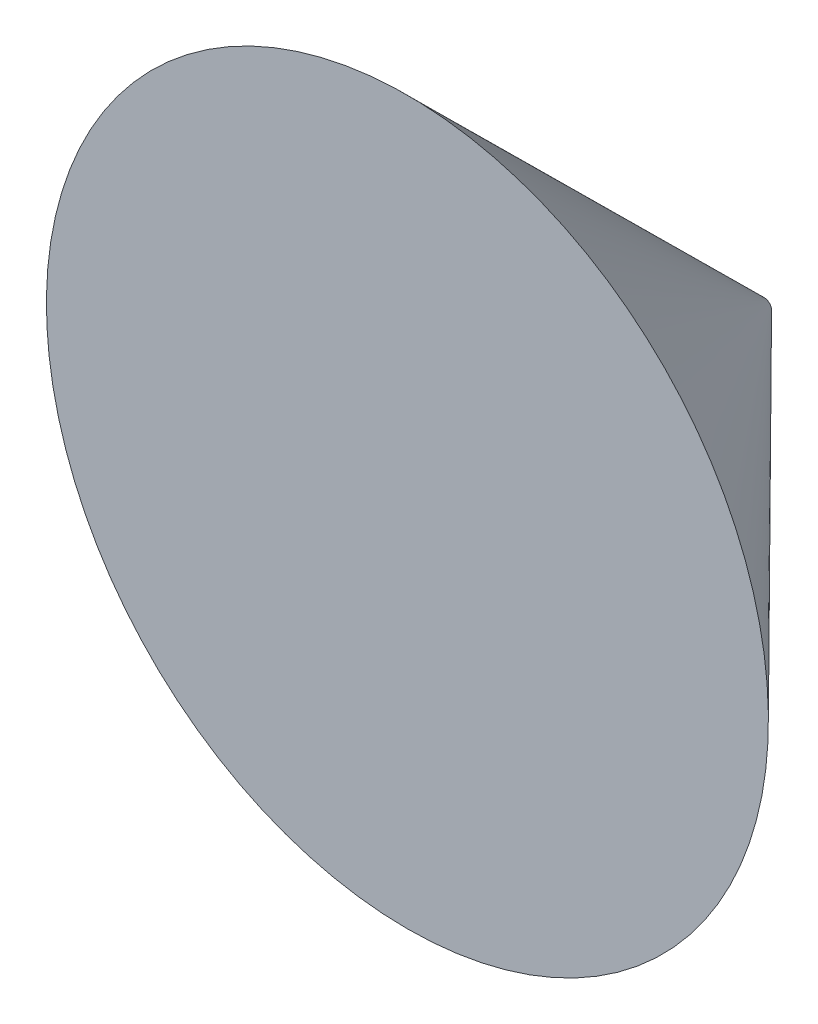
SolidWorks part; units mm, degrees
material "ABS PC"
ref_plane "Front Plane" through (0, 0, 0) normal (0, 0, 1) x (1, 0, 0)
ref_plane "Top Plane" through (0, 0, 0) normal (0, 1, 0) x (1, 0, 0)
ref_plane "Right Plane" through (0, 0, 0) normal (1, 0, 0) x (0, 0, -1)
ref_axis "X" through (-218.1267, 0, 0) along (1, 0, 0)
ref_axis "Y" through (0, 218.1267, 0) along (0, -1, 0)
ref_axis "Z" through (0, 0, -9.8) along (0, 0, 1)
sketch "Sketch1" plane through (0, 0, 0) normal (1, 0, 0) x (0, 0, -1)
  line L0 (0, 0) -> (-196, 0)
  line L1 (-196, 0) -> (-196, 198.297)
  line L2 (-196, 198.297) -> (0, 4)
  line L3 (0, 4) -> (0, 0)
  dimension "D1" = 196
  dimension "D2" = 4
  dimension "D3" = 44.75
revolve "Revolve1" add sketch "Sketch1" angle 360 about L0
